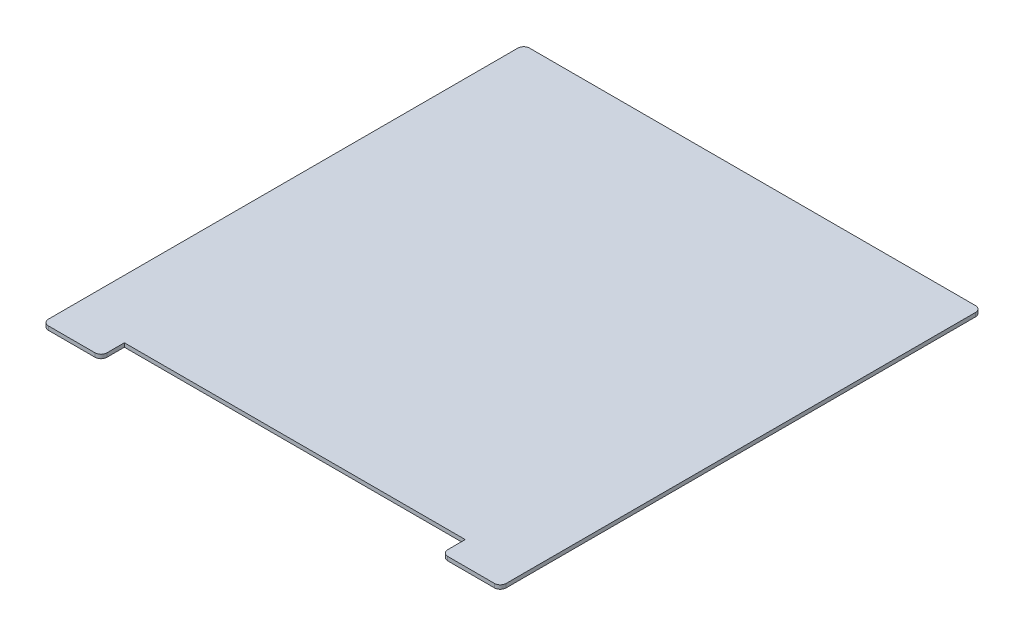
SolidWorks part; units mm, degrees
ref_plane "Front Plane" through (0, 0, 0) normal (0, 0, 1) x (1, 0, 0)
ref_plane "Top Plane" through (0, 0, 0) normal (0, 1, 0) x (1, 0, 0)
ref_plane "Right Plane" through (0, 0, 0) normal (1, 0, 0) x (0, 0, -1)
sketch "Sketch1" plane through (0, 0, 0) normal (0, 1, 0) x (1, 0, 0)
  line L0 (-175, -197.6497) -> (-175, -185.6497)
  line L1 (-205, 49.3503) -> (30, 49.3503)
  line L2 (-205, 49.3503) -> (-205, -197.6497)
  line L3 (-205, -197.6497) -> (-175, -197.6497)
  line L4 (30, 49.3503) -> (30, -197.6497)
  line L5 (-175, -185.6497) -> (0, -185.6497)
  line L6 (0, -185.6497) -> (0, -197.6497)
  line L7 (0, -197.6497) -> (30, -197.6497)
  dimension "D1" = 235
  dimension "D2" = 247
  dimension "D3" = 235
  dimension "D4" = 30
  dimension "D5" = 30
extrude "Boss-Extrude1" add sketch "Sketch1" along normal blind 2
fillet "Fillet1" radius 3 6 edges at (30, 1, -49.3503) (-205, 1, -49.3503) (-175, 1, 197.6497) (-205, 1, 197.6497) (30, 1, 197.6497) (0, 1, 197.6497)
